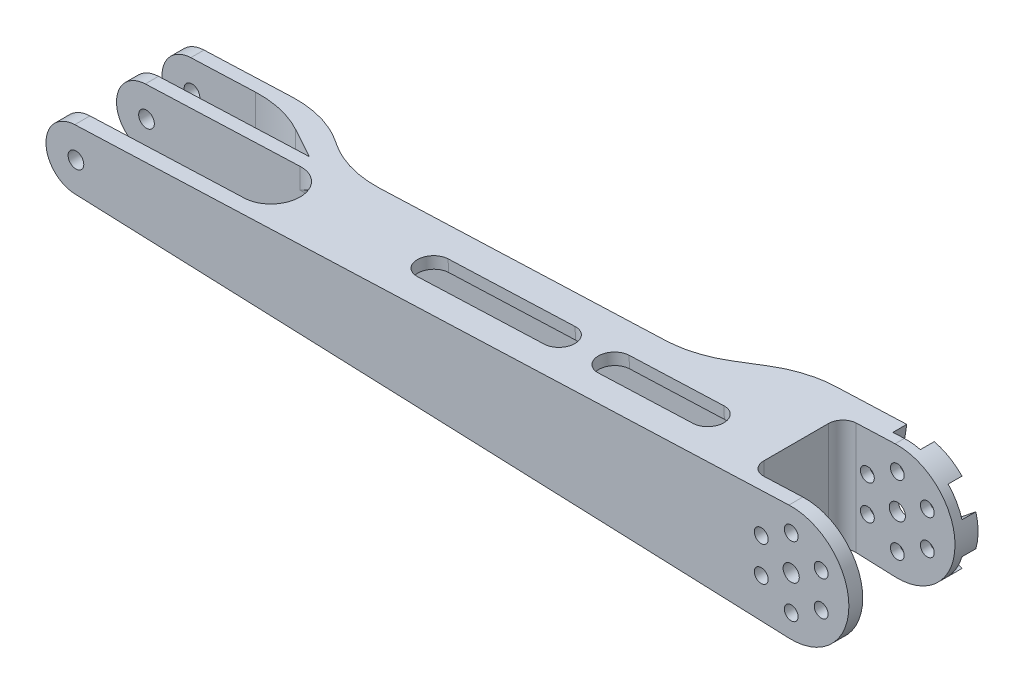
SolidWorks part; units mm, degrees
ref_plane "前视基准面" through (0, 0, 0) normal (0, 0, 1) x (1, 0, 0)
ref_plane "上视基准面" through (0, 0, 0) normal (0, 1, 0) x (1, 0, 0)
ref_plane "右视基准面" through (0, 0, 0) normal (1, 0, 0) x (0, 0, -1)
sketch "草图2" plane through (0, 0, 0) normal (0, 0, 1) x (1, 0, 0)
  line L0 (0, 0) -> (-155, 0) construction
  line L1 (-155.2516, -6.4951) -> (-0.4839, -12.4906)
  line L2 (-155.2516, 6.4951) -> (-0.4839, 12.4906)
  arc A0 (-0.4839, -12.4906) -> (-0.4839, 12.4906) centre (0, 0) ccw
  arc A1 (-155.2516, 6.4951) -> (-155.2516, -6.4951) centre (-155, 0) ccw
  circle A2 centre (-6.4952, 3.75) radius 1.5
  circle A3 centre (0, 7.5) radius 1.5
  circle A4 centre (6.4952, 3.75) radius 1.5
  circle A5 centre (6.4952, -3.75) radius 1.5
  circle A6 centre (0, -7.5) radius 1.5
  circle A7 centre (-6.4952, -3.75) radius 1.5
  circle A8 centre (0, 0) radius 1.75
  point P23 (0, 0)
  dimension "D1" = 13
  dimension "D2" = 25
  dimension "D3" = 155
  dimension "D4" = 6
extrude "凸台-拉伸1" add sketch "草图2" along normal blind 25
sketch "草图3" plane through (0, 0, 0) normal (0, 0, -1) x (-1, 0, 0)
  line L14 (155.2516, 6.4951) -> (0.4839, 12.4906)
  line L15 (0.4839, -12.4906) -> (155.2516, -6.4951)
  line L16 (155.2516, 6.4951) -> (2.9576, 12.3948)
  line L17 (2.9576, -12.3948) -> (155.2516, -6.4951)
  line L24 (10.4181, 9.2102) -> (3.8438, 6.6576)
  line L25 (7.6876, 0) -> (13.1853, 4.4173)
  line L26 (13.1853, -4.4173) -> (7.6876, 0)
  line L27 (3.8438, -6.6576) -> (10.4181, -9.2102)
  line L28 (2.7672, -13.6274) -> (3.8438, -6.6576)
  line L29 (-3.8438, -6.6576) -> (-2.7672, -13.6274)
  line L30 (-10.4181, -9.2102) -> (-3.8438, -6.6576)
  line L31 (-7.6876, 0) -> (-13.1853, -4.4173)
  line L32 (-13.1853, 4.4173) -> (-7.6876, 0)
  line L33 (-3.8438, 6.6576) -> (-10.4181, 9.2102)
  line L34 (-2.7672, 13.6274) -> (-3.8438, 6.6576)
  line L35 (3.8438, 6.6576) -> (2.7672, 13.6274)
  line L36 (10.4181, 9.2102) -> (3.8438, 6.6576)
  line L37 (7.6876, 0) -> (13.1853, 4.4173)
  line L38 (13.1853, -4.4173) -> (7.6876, 0)
  line L39 (3.8438, -6.6576) -> (10.4181, -9.2102)
  line L40 (2.9576, -12.3948) -> (3.8438, -6.6576)
  line L41 (-3.8438, -6.6576) -> (-2.9977, -12.1352)
  line L42 (-9.0106, -8.6637) -> (-3.8438, -6.6576)
  line L43 (-7.6876, 0) -> (-12.0083, -3.4716)
  line L44 (-12.0083, 3.4716) -> (-7.6876, 0)
  line L45 (-3.8438, 6.6576) -> (-9.0106, 8.6637)
  line L46 (-2.9977, 12.1352) -> (-3.8438, 6.6576)
  line L47 (3.8438, 6.6576) -> (2.9576, 12.3948)
  arc A6 (-9.0106, -8.6637) -> (-2.9977, -12.1352) centre (0, 0) ccw
  arc A7 (-12.0083, 3.4716) -> (-12.0083, -3.4716) centre (0, 0) ccw
  arc A8 (155.2516, -6.4951) -> (155.2516, 6.4951) centre (155, 0) ccw
  arc A9 (0.4839, 12.4906) -> (0.4839, -12.4906) centre (0, 0) ccw
  arc A10 (155.2516, -6.4951) -> (155.2516, 6.4951) centre (155, 0) ccw
  arc A11 (-2.9977, 12.1352) -> (-9.0106, 8.6637) centre (0, 0) ccw
  arc A12 (13.1853, 4.4173) -> (10.4181, 9.2102) centre (11.4315, 6.6) ccw
  arc A13 (10.4181, -9.2102) -> (13.1853, -4.4173) centre (11.4315, -6.6) ccw
  arc A14 (-2.7672, -13.6274) -> (2.7672, -13.6274) centre (0, -13.2) ccw
  arc A15 (-13.1853, -4.4173) -> (-10.4181, -9.2102) centre (-11.4315, -6.6) ccw
  arc A16 (-10.4181, 9.2102) -> (-13.1853, 4.4173) centre (-11.4315, 6.6) ccw
  arc A17 (2.7672, 13.6274) -> (-2.7672, 13.6274) centre (0, 13.2) ccw
  arc A18 (13.1853, 4.4173) -> (10.4181, 9.2102) centre (11.4315, 6.6) ccw
  arc A19 (10.4181, -9.2102) -> (13.1853, -4.4173) centre (11.4315, -6.6) ccw
  dimension "D1" = 0.3
  dimension "D2" = 0
extrude "凸台-拉伸2" add sketch "草图3" along normal blind 3
sketch "草图4" plane through (0, 0, 0) normal (0, 1, 0) x (1, 0, 0)
  line L0 (-11.9484, -5) -> (-11.9484, -19)
  line L1 (12.751, -22) -> (-8.9484, -22)
  line L2 (12.751, -22) -> (12.751, -2)
  line L3 (12.751, -2) -> (-8.9484, -2)
  line L6 (-155.2516, 3) -> (-2.9576, 3) construction
  line L9 (-0.4839, -25) -> (12.5, -25) construction
  arc A0 (-8.9484, -22) -> (-11.9484, -19) centre (-8.9484, -19) cw
  arc A1 (-8.9484, -2) -> (-11.9484, -5) centre (-8.9484, -5) ccw
  dimension "D3" = 3
  dimension "D1" = 5
  dimension "D2" = 3
extrude "切除-拉伸1" cut sketch "草图4" against normal mid plane 56
sketch "草图5" plane through (0, 0, 0) normal (0, 1, 0) x (1, 0, 0)
  line L0 (-120.0054, -15.7106) -> (-172.3533, -15.7106) construction
  line L1 (-155, -15.7106) -> (0, -15.7106) construction
  line L3 (-217.2197, -21.7106) -> (-16.2988, -21.7106)
  line L4 (-217.2197, -21.7106) -> (-217.2197, -9.7106)
  line L5 (-217.2197, -9.7106) -> (-16.2988, -9.7106)
  line L6 (-16.2988, -21.7106) -> (-16.2988, -9.7106)
  line L7 (-217.2197, -21.7106) -> (-16.2988, -9.7106) construction
  line L8 (-217.2197, -9.7106) -> (-16.2988, -21.7106) construction
  point P4 (-116.7592, -15.7106)
extrude "切除-拉伸2" cut sketch "草图5" against normal mid plane 56
sketch "草图6" plane through (0, 0, 0) normal (0, 1, 0) x (1, 0, 0)
  line L0 (-155.2516, -3.3553) -> (-95.9366, -3.3553) construction
  line L1 (-155.2516, -9.7106) -> (-155.2516, 3) construction
  line L2 (-134.9001, 0.1447) -> (-122.5688, -6.8553)
  line L3 (-175.6031, 0.1447) -> (-134.9001, 0.1447)
  line L4 (-175.6031, 0.1447) -> (-175.6031, -6.8553)
  line L5 (-175.6031, -6.8553) -> (-134.9001, -6.8553)
  line L6 (-122.5688, -6.8553) -> (-134.9001, -6.8553)
  line L7 (-175.6031, 0.1447) -> (-134.9001, -6.8553) construction
  line L8 (-175.6031, -6.8553) -> (-134.9001, 0.1447) construction
  line L9 (-128.7128, 3) -> (-115.9002, -5.7106)
  line L10 (-2.9576, 3) -> (-155.2516, 3) construction
  line L11 (-115.9002, -5.7106) -> (-40.3892, -5.7106)
  line L12 (-40.3892, -5.7106) -> (-24.5135, 3)
  line L13 (-24.5135, 3) -> (-128.7128, 3)
  line L14 (-16.2988, -9.7106) -> (-155.2516, -9.7106) construction
  dimension "D1" = 7
  dimension "D2" = 4
extrude "切除-拉伸3" cut sketch "草图6" against normal mid plane 56
fillet "圆角1" radius 24 5 edges at (-134.9001, 0, -0.1447) (-128.7128, 0, -3) (-115.9002, 0, 5.7106) (-40.3892, 0, 5.7106) (-24.5135, 0, -3)
sketch "草图9" plane through (0, 0, 9.7106) normal (0, 0, 1) x (1, 0, 0)
  line L1 (-121.8208, 7.7902) -> (-16.2988, 11.878)
  line L2 (-0.4839, 12.4906) -> (-155.2516, 6.4951) construction
  line L3 (-155.2516, 6.4951) -> (-16.2988, 11.878) construction
extrude "拉伸-薄壁1" add sketch "草图9" along normal up to surface (12 mm away) thin up to face at (-87.3373, 0, 21.7106) thin type one direction wall 2.5
fillet "圆角2" radius 5 2 edges at (-16.2988, -1.2509, 21.7106) (-16.2988, -1.2509, 9.7106)
sketch "草图10" plane through (-0.3871, 9.9925, 0) normal (0.0387, -0.9993, 0) x (0.9993, 0.0387, 0)
  line L0 (-47.3109, 15.7106) -> (-26.7429, 15.7106) construction
  line L1 (19.648, 15.7106) -> (-99.525, 15.7106) construction
  line L2 (-47.3109, 19.0419) -> (-26.7429, 19.0419)
  line L3 (-47.3109, 12.3793) -> (-26.7429, 12.3793)
  line L4 (-86.5484, 15.7106) -> (-59.0189, 15.7106) construction
  line L5 (-86.5484, 19.0419) -> (-59.0189, 19.0419)
  line L6 (-86.5484, 12.3793) -> (-59.0189, 12.3793)
  arc A0 (-47.3109, 19.0419) -> (-47.3109, 12.3793) centre (-47.3109, 15.7106) ccw
  arc A1 (-26.7429, 12.3793) -> (-26.7429, 19.0419) centre (-26.7429, 15.7106) ccw
  arc A2 (-86.5484, 19.0419) -> (-86.5484, 12.3793) centre (-86.5484, 15.7106) ccw
  arc A3 (-59.0189, 12.3793) -> (-59.0189, 19.0419) centre (-59.0189, 15.7106) ccw
  point P4 (-37.0269, 15.7106)
  point P9 (-72.7836, 15.7106)
extrude "切除-拉伸4" cut sketch "草图10" against normal blind 56
sketch "草图11" plane through (0, 0, 0) normal (0, 1, 0) x (1, 0, 0)
  line L0 (-121.724, -9.7106) -> (-128.4101, -9.7106)
  line L1 (-155.2516, -9.7106) -> (-121.8208, -9.7106) construction
  line L2 (-128.4101, -9.7106) -> (-128.4101, -21.7106)
  line L3 (-121.8208, -21.7106) -> (-155.2516, -21.7106) construction
  line L4 (-128.4101, -21.7106) -> (-121.724, -21.7106)
  arc A0 (-121.724, -9.7106) -> (-121.724, -21.7106) centre (-121.724, -15.7106) cw
extrude "切除-拉伸5" cut sketch "草图11" along normal blind 56
fillet "圆角3" radius 2 5 edges at (-71.5114, 7.2372, 21.7106) (-17.7632, 9.3194, 20.2461) (-16.2988, 9.3761, 15.7106) (-17.7632, 9.3194, 11.1751) (-71.5114, 7.2372, 9.7106)
sketch "草图12" plane through (0, 0, 0) normal (0, 0, 1) x (1, 0, 0)
  circle A0 centre (-155, 0) radius 1.7
extrude "切除-拉伸6" cut sketch "草图12" against normal mid plane 56
